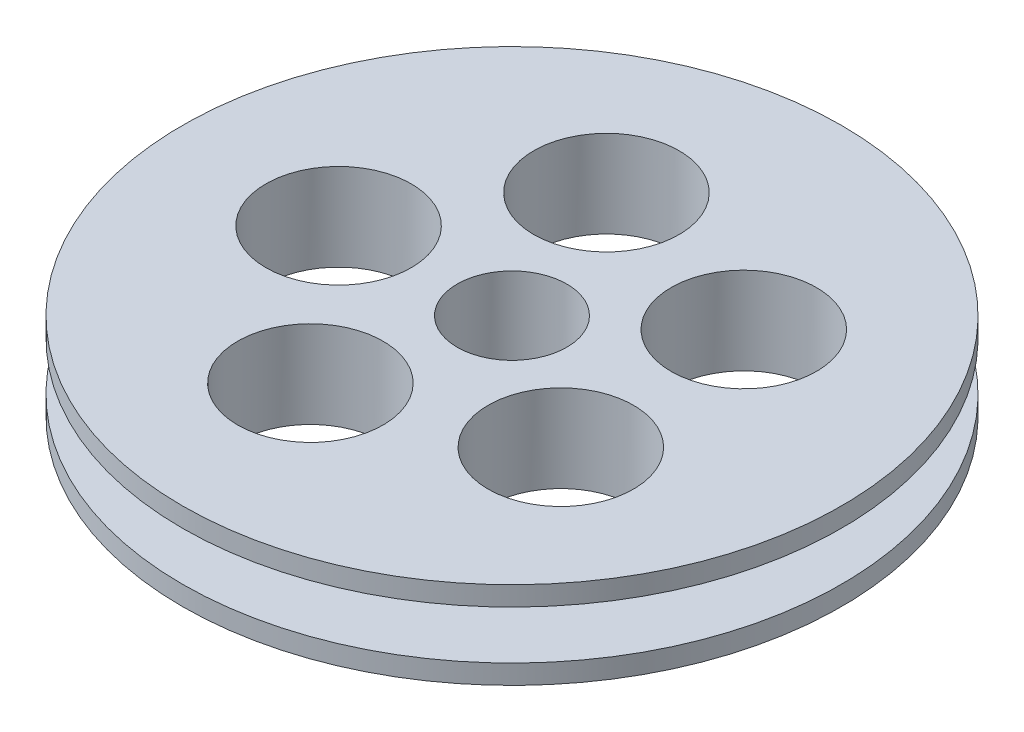
SolidWorks part; units mm, degrees
ref_plane "Front Plane" through (0, 0, 0) normal (0, 0, 1) x (1, 0, 0)
ref_plane "Top Plane" through (0, 0, 0) normal (0, 1, 0) x (1, 0, 0)
ref_plane "Right Plane" through (0, 0, 0) normal (1, 0, 0) x (0, 0, -1)
sketch "Sketch1" plane through (0, 0, 0) normal (1, 0, 0) x (0, 0, -1)
  line L0 (0, 2.5) -> (-4, 2.5) construction
  line L1 (0, 0) -> (30, 0)
  line L2 (0, 0) -> (0, -2)
  line L3 (0, -2) -> (30, -2)
  line L4 (30, 0) -> (30, -2)
  line L5 (0, 0) -> (22, 0)
  line L6 (0, 0) -> (0, 5)
  line L7 (0, 5) -> (22, 5)
  line L8 (22, 0) -> (22, 5)
  line L9 (0, 5) -> (30, 5)
  line L10 (0, 5) -> (0, 7)
  line L11 (0, 7) -> (30, 7)
  line L12 (30, 5) -> (30, 7)
  line L13 (-4, 2.5) -> (-4, 20.0021) construction
  dimension "D1" = 2
  dimension "D2" = 5
  dimension "D3" = 30
  dimension "D4" = 22
  dimension "D5" = 4
revolve "Revolve4" add sketch "Sketch1" angle 360 about L13 region at (0, 2.5, -11) region at (0, -1, -15) region at (0, 6, -15)
sketch "Sketch3" plane through (0, 7, 0) normal (0, 1, 0) x (1, 0, 0)
  circle A0 centre (0, -4) radius 5.6537
  circle A1 centre (0, -4) radius 4 construction
  circle A2 centre (-16.9752, -4.9176) radius 7.5
  circle A3 centre (-6.1183, 11.8608) radius 7.5
  circle A4 centre (13.1939, 6.7201) radius 7.5
  circle A5 centre (14.2726, -13.2354) radius 7.5
  circle A6 centre (-4.373, -20.4279) radius 7.5
  point P6 (0, -4)
  point P17 (0, -4)
  dimension "D2" = 15
  dimension "D1" = 17
  dimension "D3" = 5
extrude "Cut-Extrude1" cut sketch "Sketch3" against normal blind 10
